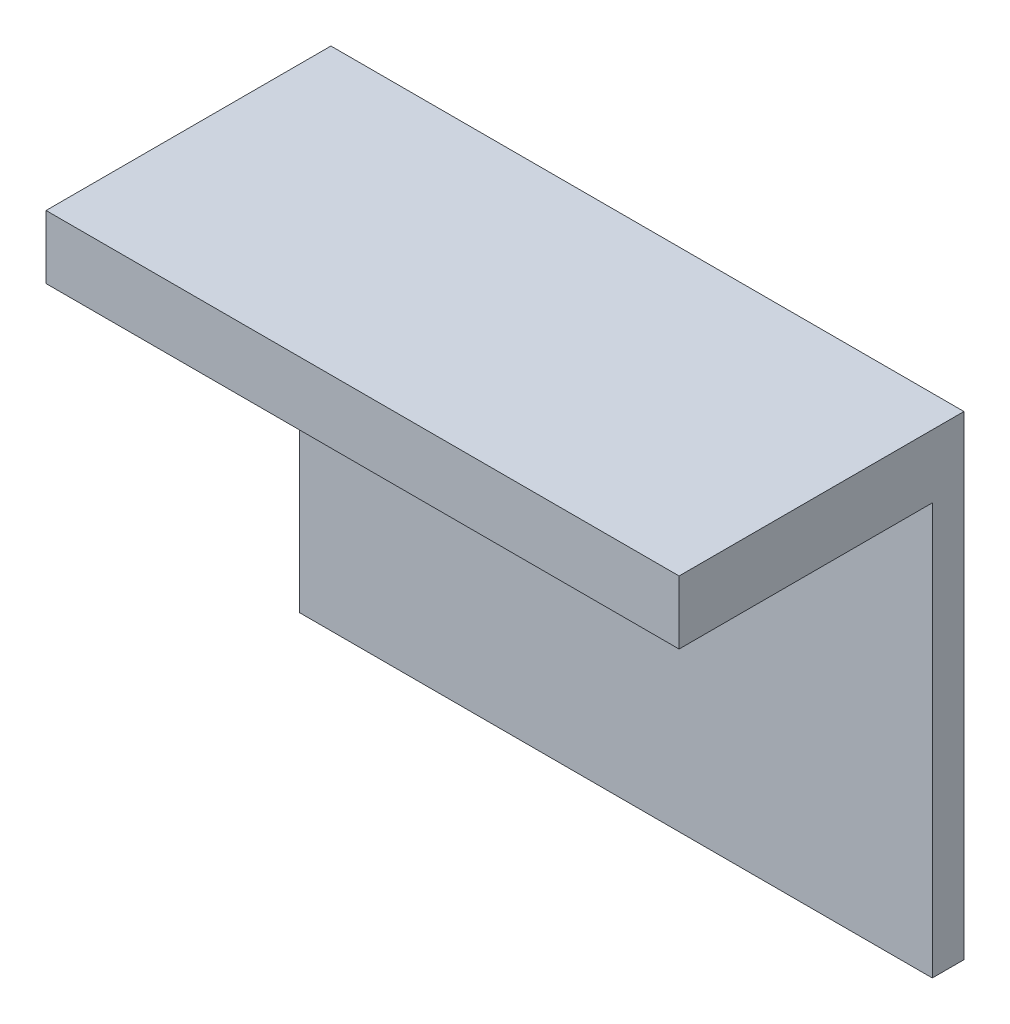
SolidWorks part; units mm, degrees
ref_plane "Plano frontal" through (0, 0, 0) normal (0, 0, 1) x (1, 0, 0)
ref_plane "Plano superior" through (0, 0, 0) normal (0, 1, 0) x (1, 0, 0)
ref_plane "Plano direito" through (0, 0, 0) normal (1, 0, 0) x (0, 0, -1)
sketch "Esboço1" plane through (0, 0, 0) normal (0, 0, 1) x (1, 0, 0)
  line L1 (-10, -7.5) -> (10, -7.5)
  line L2 (-10, -7.5) -> (-10, 7.5)
  line L3 (-10, 7.5) -> (10, 7.5)
  line L4 (10, -7.5) -> (10, 7.5)
  line L5 (-10, -7.5) -> (10, 7.5) construction
  line L6 (-10, 7.5) -> (10, -7.5) construction
  point P0 (0, 0)
  dimension "D1" = 15
  dimension "D2" = 20
extrude "Ressalto-extrusão1" add sketch "Esboço1" along normal mid plane 1
sketch "Esboço2" plane through (0, 0, 0.5) normal (0, 0, 1) x (1, 0, 0)
  line L0 (0, 0) -> (0, 7.5) construction
  line L1 (10, 7.5) -> (-10, 7.5) construction
  line L2 (-10, 7.5) -> (-10, 5.5)
  line L3 (-10, 7.5) -> (-10, -7.5) construction
  line L4 (-10, 5.5) -> (10, 5.5)
  line L5 (10, -7.5) -> (10, 7.5) construction
  line L6 (10, 5.5) -> (10, 7.5)
  line L7 (10, 7.5) -> (-10, 7.5)
  dimension "D1" = 2
extrude "Ressalto-extrusão2" add sketch "Esboço2" along normal blind 8
sketch "Esboço3" plane through (0, 0, -0.5) normal (0, 0, -1) x (-1, 0, 0)
  line L10 (-10, 0) -> (10, 0) construction
  line L11 (10, 7.5) -> (10, -7.5) construction
  text T0 "FRENTE"
  point P5 (0, 0)
extrude "Corte-extrusão1" cut sketch "Esboço3" against normal blind 0.5
